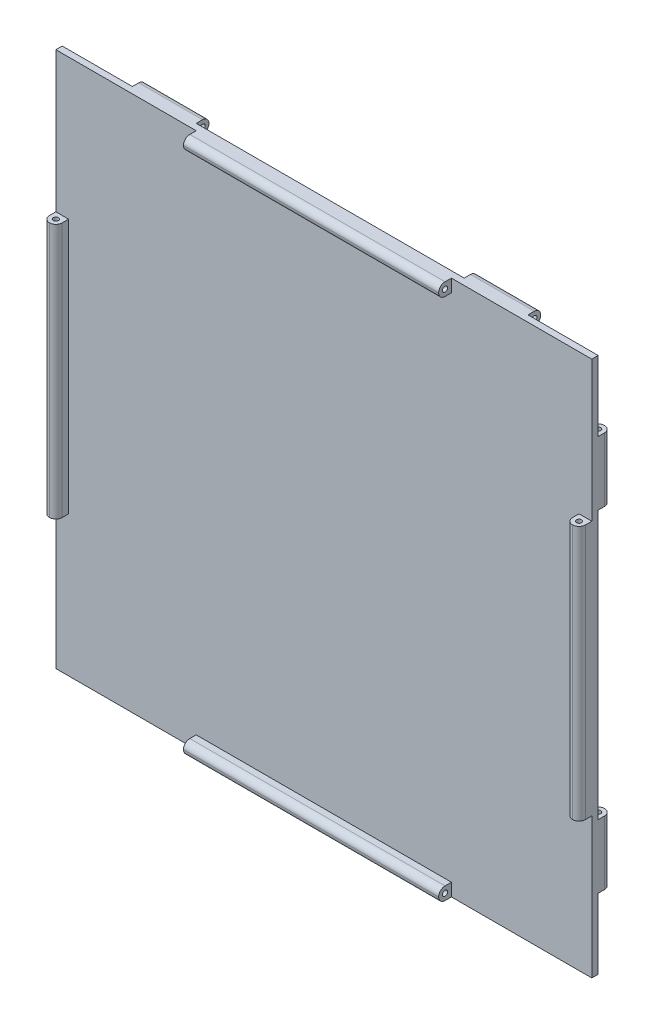
SolidWorks part; units mm, degrees
ref_plane "前视基准面" through (0, 0, 0) normal (0, 0, 1) x (1, 0, 0)
ref_plane "上视基准面" through (0, 0, 0) normal (0, 1, 0) x (1, 0, 0)
ref_plane "右视基准面" through (0, 0, 0) normal (1, 0, 0) x (0, 0, -1)
sketch "草图1" plane through (0, 0, 0) normal (0, 0, 1) x (1, 0, 0)
  line L1 (210, -210) -> (-210, -210)
  line L2 (210, -210) -> (210, 210)
  line L3 (210, 210) -> (-210, 210)
  line L4 (-210, -210) -> (-210, 210)
  line L5 (210, -210) -> (-210, 210) construction
  line L6 (210, 210) -> (-210, -210) construction
  point P0 (0, 0)
  dimension "D1" = 420
  dimension "D2" = 420
extrude "凸台-拉伸1" add sketch "草图1" along normal blind 5
sketch "草图3" plane through (0, 0, 0) normal (0, 0, -1) x (-1, 0, 0)
  line L0 (-210, 0) -> (210, 0) construction
  line L1 (-155, -200) -> (-105, -200)
  line L2 (-155, -200) -> (-155, -210)
  line L3 (-155, -210) -> (-105, -210)
  line L4 (210, -210) -> (210, 210)
  line L5 (210, 210) -> (-210, 210)
  line L6 (-210, 210) -> (-210, -210)
  line L7 (-210, -210) -> (210, -210)
  line L8 (210, -210) -> (210, 210)
  line L9 (210, 210) -> (-210, 210)
  line L10 (-210, 210) -> (-210, -210)
  line L11 (-210, -210) -> (210, -210)
  line L12 (-105, -200) -> (-105, -210)
  line L13 (105, -200) -> (155, -200)
  line L14 (105, -200) -> (105, -210)
  line L15 (105, -210) -> (155, -210)
  line L16 (155, -200) -> (155, -210)
  line L17 (0, 210) -> (0, -210) construction
  line L19 (-155, 210) -> (-105, 210)
  line L20 (-155, 210) -> (-155, 200)
  line L21 (-155, 200) -> (-105, 200)
  line L22 (-105, 210) -> (-105, 200)
  line L23 (105, 210) -> (155, 210)
  line L24 (105, 210) -> (105, 200)
  line L25 (105, 200) -> (155, 200)
  line L26 (155, 210) -> (155, 200)
  line L27 (-210, 155) -> (-200, 155)
  line L28 (-210, 155) -> (-210, 105)
  line L29 (-210, 105) -> (-200, 105)
  line L30 (-200, 155) -> (-200, 105)
  line L31 (-210, -105) -> (-200, -105)
  line L32 (-210, -105) -> (-210, -155)
  line L33 (-210, -155) -> (-200, -155)
  line L34 (-200, -105) -> (-200, -155)
  line L35 (210, 155) -> (200, 155)
  line L36 (210, 155) -> (210, 105)
  line L37 (210, 105) -> (200, 105)
  line L38 (200, 155) -> (200, 105)
  line L39 (210, -105) -> (200, -105)
  line L40 (210, -105) -> (210, -155)
  line L41 (210, -155) -> (200, -155)
  line L42 (200, -105) -> (200, -155)
  point P12 (-155, -205)
  line M14 (-210, -210) -> (210, -210)
  dimension "D2" = 50
  dimension "D3" = 10
  dimension "D4" = 50
  dimension "D5" = 10
  dimension "D6" = 55
  dimension "D7" = 55
  dimension "D8" = 55
  dimension "D9" = 50
  dimension "D10" = 10
  dimension "D11" = 55
  dimension "D12" = 50
  dimension "D13" = 10
  dimension "D1" = 0
extrude "凸台-拉伸2" add sketch "草图3" along normal blind 10 contours L12 L1 L2 M14 | L34 L31 L10 L33 | L30 L27 L10 L29 | L22 L9 L20 L21 | L35 L38 L37 L8 | L26 L9 L24 L25 | L39 L42 L41 L8 | L16 L13 L14 L11 region at (130, -205, 0) region at (-130, -205, 0) region at (205, -130, 0) region at (205, 130, 0) region at (-205, -130, 0) region at (-205, 130, 0) region at (130, 205, 0) region at (-130, 205, 0)
sketch "草图4" plane through (0, 0, 5) normal (0, 0, 1) x (1, 0, 0)
  line L0 (-210, -210) -> (210, -210) construction
  line L1 (100, -210) -> (-100, -210)
  line L2 (100, -210) -> (100, -200)
  line L3 (100, -200) -> (-100, -200)
  line L4 (-100, -210) -> (-100, -200)
  line L5 (210, -210) -> (210, 210) construction
  line L6 (210, -100) -> (200, -100)
  line L7 (210, -100) -> (210, 100)
  line L8 (210, 100) -> (200, 100)
  line L9 (200, -100) -> (200, 100)
  line L10 (210, 210) -> (-210, 210) construction
  line L11 (100, 200) -> (-100, 200)
  line L12 (100, 200) -> (100, 210)
  line L13 (100, 210) -> (-100, 210)
  line L14 (-100, 200) -> (-100, 210)
  line L15 (-210, 210) -> (-210, -210) construction
  line L16 (-200, -100) -> (-210, -100)
  line L17 (-200, -100) -> (-200, 100)
  line L18 (-200, 100) -> (-210, 100)
  line L19 (-210, -100) -> (-210, 100)
  dimension "D1" = 10
  dimension "D2" = 10
  dimension "D3" = 10
  dimension "D4" = 10
  dimension "D5" = 200
  dimension "D6" = 110
  dimension "D7" = 110
  dimension "D8" = 200
extrude "凸台-拉伸3" add sketch "草图4" along normal blind 10 contours L7 L6 L9 L8 | L2 L1 L4 L3 | L17 L16 L19 L18 | L12 L11 L14 L13
fillet "圆角1" radius 5 24 edges at (-210, 0, 15) (-200, 0, 15) (0, -210, 15) (0, -200, 15) (0, 200, 15) (0, 210, 15) (200, 0, 15) (210, 0, 15) (200, -130, -10) (210, -130, -10) (130, 210, -10) (130, 200, -10) (200, 130, -10) (210, 130, -10) (-130, -210, -10) (-130, -200, -10) (-130, 210, -10) (-130, 200, -10) (-210, 130, -10) (-200, 130, -10) (-210, -130, -10) (-200, -130, -10) (130, -210, -10) (130, -200, -10)
sketch "草图5" plane through (0, 155, 0) normal (0, 1, 0) x (1, 0, 0)
  circle A0 centre (205, 5) radius 2
  dimension "D1" = 4
extrude "切除-拉伸1" cut sketch "草图5" against normal through all
sketch "草图6" plane through (0, 100, 0) normal (0, 1, 0) x (1, 0, 0)
  line L0 (200, -10) -> (210, -10) construction
  circle A0 centre (205, -10) radius 2
  dimension "D1" = 4
extrude "切除-拉伸2" cut sketch "草图6" against normal through all
sketch "草图7" plane through (155, 0, 0) normal (1, 0, 0) x (0, 0, -1)
  circle A2 centre (5, -205) radius 2
  dimension "D1" = 4
extrude "切除-拉伸3" cut sketch "草图7" against normal through all both and the other way through all
sketch "草图8" plane through (100, 0, 0) normal (1, 0, 0) x (0, 0, -1)
  circle A0 centre (-10, -205) radius 2
  dimension "D1" = 4
extrude "切除-拉伸4" cut sketch "草图8" against normal through all contours A0
sketch "草图9" plane through (0, -155, 0) normal (0, -1, 0) x (1, 0, 0)
  circle A0 centre (-205, -5) radius 2
  dimension "D1" = 4
extrude "切除-拉伸5" cut sketch "草图9" against normal through all both and the other way through all
sketch "草图10" plane through (0, -100, 0) normal (0, -1, 0) x (1, 0, 0)
  circle A0 centre (-205, 10) radius 2
  dimension "D1" = 4
extrude "切除-拉伸6" cut sketch "草图10" against normal through all contours A0
sketch "草图11" plane through (-155, 0, 0) normal (-1, 0, 0) x (0, 0, 1)
  circle A0 centre (-5, 205) radius 2
  dimension "D1" = 4
extrude "切除-拉伸7" cut sketch "草图11" against normal through all both and the other way through all
sketch "草图12" plane through (-100, 0, 0) normal (-1, 0, 0) x (0, 0, 1)
  circle A0 centre (10, 205) radius 2
  dimension "D1" = 4
extrude "切除-拉伸8" cut sketch "草图12" against normal through all
scale "缩放比例1" scale about origin uniform scaling yes scale factor 0.5
